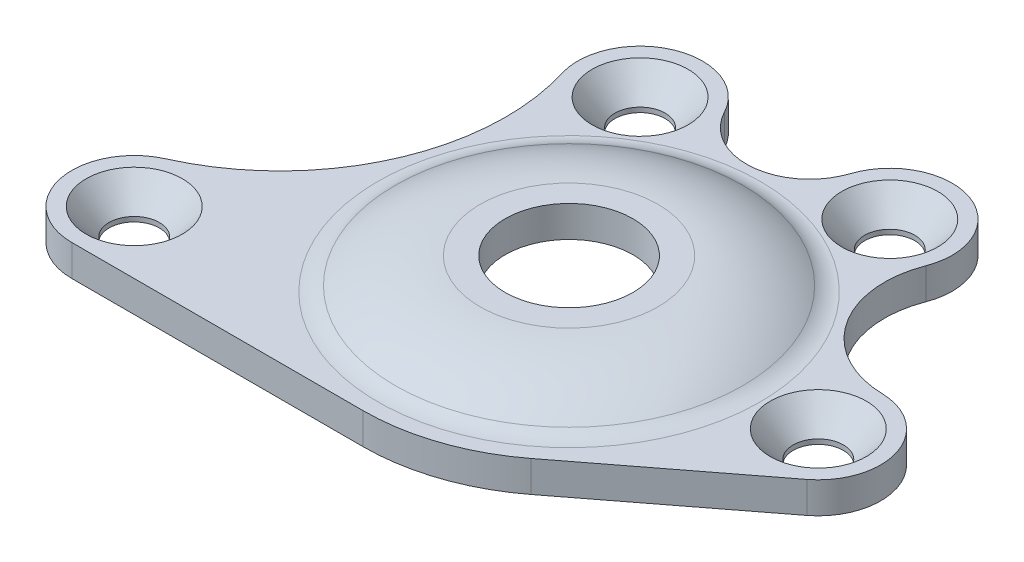
SolidWorks part; units mm, degrees
material "Alum Plate"
ref_plane "Front Plane" through (0, 0, 0) normal (0, 0, 1) x (1, 0, 0)
ref_plane "Top Plane" through (0, 0, 0) normal (0, 1, 0) x (1, 0, 0)
ref_plane "Right Plane" through (0, 0, 0) normal (1, 0, 0) x (0, 0, -1)
sketch "Top Layout" plane through (0, 0, 0) normal (0, 1, 0) x (1, 0, 0)
  line L0 (-114.046, -123.825) -> (-104.775, -123.825) construction
  line L1 (-104.775, -142.875) -> (-101.6, -142.875)
  line L2 (-104.775, -142.875) -> (-104.775, -104.775)
  line L3 (-104.775, -104.775) -> (-101.6, -104.775)
  line L4 (-101.6, -142.875) -> (-101.6, -104.775)
  line L5 (-104.775, -142.875) -> (-101.6, -104.775) construction
  line L6 (-104.775, -104.775) -> (-101.6, -142.875) construction
  line L7 (-19.05, -105.8164) -> (-101.6, -105.8164)
  line L8 (-19.05, -105.8164) -> (-19.05, -141.8336)
  line L9 (-19.05, -141.8336) -> (-101.6, -141.8336)
  line L10 (-101.6, -105.8164) -> (-101.6, -141.8336)
  line L11 (-19.05, -105.8164) -> (-101.6, -141.8336) construction
  line L12 (-19.05, -141.8336) -> (-101.6, -105.8164) construction
  line L13 (-133.096, -85.725) -> (-114.046, -85.725)
  line L14 (-133.096, -85.725) -> (-133.096, -161.925)
  line L15 (-133.096, -161.925) -> (-114.046, -161.925)
  line L16 (-114.046, -85.725) -> (-114.046, -161.925)
  line L17 (-133.096, -85.725) -> (-114.046, -161.925) construction
  line L18 (-133.096, -161.925) -> (-114.046, -85.725) construction
  line L19 (-104.775, -123.825) -> (0, -123.825) construction
  line L20 (0, -123.825) -> (0, 0) construction
  line L21 (-52.3528, -40.1717) -> (0, 0) construction
  line L22 (-70.6449, -16.3328) -> (-18.2922, 23.8388)
  line L23 (-34.0606, -64.0105) -> (18.2922, -23.8388)
  line L24 (-30.9251, 40.3023) -> (-122.2248, -29.7544)
  line L25 (-153.9748, -53.975) -> (-153.9748, -123.825)
  line L26 (-109.5248, -162.052) -> (109.5248, -162.052)
  line L27 (0, -162.052) -> (0, -123.825) construction
  line L28 (-109.5248, -162.052) -> (-109.5248, -20.0093) construction
  line L29 (-104.775, -142.875) -> (-104.775, -152.527)
  line L30 (-104.775, -152.527) -> (104.775, -152.527)
  line L31 (104.775, -104.775) -> (101.6, -104.775)
  line L32 (-144.4498, -73.025) -> (-109.5248, -73.025)
  line L33 (-144.4498, -73.025) -> (-144.4498, -123.825)
  line L34 (-144.4498, -123.825) -> (-109.5248, -123.825) construction
  line L35 (-109.5248, -73.025) -> (-109.5248, -162.052)
  line L36 (-144.4498, -73.025) -> (-109.5248, -123.825) construction
  line L37 (-144.4498, -123.825) -> (-109.5248, -73.025) construction
  line L38 (101.6, -142.875) -> (101.6, -104.775)
  line L39 (104.775, -142.875) -> (101.6, -142.875)
  line L40 (104.775, -142.875) -> (104.775, -104.775)
  line L41 (104.775, -142.875) -> (104.775, -152.527)
  line L42 (109.5248, -162.052) -> (109.5248, -20.0093) construction
  line L43 (30.9251, 40.3023) -> (122.2248, -29.7544)
  line L45 (19.05, -141.8336) -> (101.6, -141.8336)
  line L46 (101.6, -105.8164) -> (101.6, -141.8336)
  line L47 (19.05, -105.8164) -> (101.6, -105.8164)
  line L48 (19.05, -105.8164) -> (19.05, -141.8336)
  line L49 (133.096, -161.925) -> (114.046, -161.925)
  line L50 (114.046, -85.725) -> (114.046, -161.925)
  line L51 (133.096, -85.725) -> (114.046, -85.725)
  line L52 (133.096, -85.725) -> (133.096, -161.925)
  line L53 (144.4498, -123.825) -> (109.5248, -123.825) construction
  line L54 (109.5248, -73.025) -> (109.5248, -162.052)
  line L55 (144.4498, -73.025) -> (109.5248, -73.025)
  line L56 (144.4498, -73.025) -> (144.4498, -123.825)
  line L57 (-109.5248, -123.825) -> (-109.5248, -162.052) construction
  line L62 (-153.9748, -53.975) -> (-122.2248, -53.975)
  line L63 (-122.2248, -53.975) -> (-122.2248, -29.7544)
  line L64 (-144.4498, -123.825) -> (-153.9748, -123.825)
  line L65 (153.9748, -53.975) -> (153.9748, -123.825)
  line L66 (109.5248, -123.825) -> (109.5248, -162.052) construction
  line L67 (144.4498, -123.825) -> (153.9748, -123.825)
  line L68 (122.2248, -29.7544) -> (122.2248, -53.975)
  line L73 (-104.775, -104.775) -> (-104.775, -16.3647) construction
  line L74 (-95.25, -162.052) -> (-95.25, -9.0559) construction
  line L75 (-109.5248, -162.052) -> (-109.5248, -123.825) construction
  line L76 (109.5248, -162.052) -> (109.5248, -123.825) construction
  line L77 (122.2248, -53.975) -> (153.9748, -53.975)
  line L83 (104.775, -155.5496) -> (-104.775, -155.5496) construction
  line L88 (95.25, -162.052) -> (95.25, -9.0559) construction
  line L89 (104.775, -104.775) -> (104.775, -16.3647) construction
  line L92 (-104.775, -152.527) -> (-104.775, -162.052) construction
  line L93 (-14.605, -76.327) -> (14.605, -76.327)
  line L94 (-14.605, -76.327) -> (-14.605, -152.527)
  line L95 (-14.605, -152.527) -> (14.605, -152.527)
  line L96 (14.605, -76.327) -> (14.605, -152.527)
  line L97 (-14.605, -76.327) -> (14.605, -152.527) construction
  line L98 (-14.605, -152.527) -> (14.605, -76.327) construction
  line L99 (104.775, -152.527) -> (104.775, -162.052) construction
  line L100 (-19.05, -105.8164) -> (0, -105.8164) construction
  line L107 (0, -105.8164) -> (19.05, -105.8164) construction
  line L108 (104.775, -123.825) -> (114.046, -123.825) construction
  circle A0 centre (0, 0) radius 114.3
  circle A1 centre (0, 0) radius 6.35
  circle A2 centre (-52.3528, -40.1717) radius 17.8
  circle A3 centre (0, 0) radius 30.0482
  circle A4 centre (-52.3528, -40.1717) radius 30.0482
  arc A5 (-30.9251, 40.3023) -> (30.9251, 40.3023) centre (0, 0) cw
  point P2 (-103.1875, -123.825)
  point P7 (-60.325, -123.825)
  point P12 (-123.571, -123.825)
  point P30 (-126.9873, -98.425)
  point P35 (0, -114.427)
  point P53 (0, -152.527)
  dimension "D1" = 35.6
  dimension "D2" = 12.7
  dimension "D3" = 228.6
  dimension "D11" = 60.0964
  dimension "D12" = 50.8
  dimension "D14" = 52.5
  dimension "D4" = 3.175
  dimension "D5" = 19.05
  dimension "D6" = 76.2
  dimension "D7" = 82.55
  dimension "D8" = 38.1
  dimension "D9" = 104.775
  dimension "D10" = 18.0086
  dimension "D13" = 9.525
  dimension "D15" = 4.7498
  dimension "D16" = 9.525
  dimension "D17" = 9.652
  dimension "D18" = 50.8
  dimension "D19" = 12.446
  dimension "D20" = 65.9892
  dimension "D21" = 19.05
  dimension "D22" = 34.925
  dimension "D23" = 123.825
  dimension "D24" = 12.7
  dimension "D25" = 9.525
  dimension "D26" = 29.21
  dimension "D27" = 76.2
  dimension "D28" = 3.0226
sketch "Side Layout" plane through (0, 0, 0) normal (1, 0, 0) x (0, 0, -1)
  line L0 (0, -38.1) -> (0, 33.7344) construction
  line L1 (-114.3, -20.955) -> (114.3, -20.955)
  line L2 (-114.3, -20.955) -> (-114.3, -33.655)
  line L3 (-114.3, -33.655) -> (114.3, -33.655)
  line L4 (114.3, -20.955) -> (114.3, -33.655)
  line L5 (-114.3, -20.955) -> (114.3, -33.655) construction
  line L6 (-114.3, -33.655) -> (114.3, -20.955) construction
  line L7 (-9.525, -32.9406) -> (9.525, -32.9406)
  line L8 (-9.525, -32.9406) -> (-9.525, -38.1)
  line L9 (-9.525, -38.1) -> (9.525, -38.1)
  line L10 (9.525, -32.9406) -> (9.525, -38.1)
  line L11 (-9.525, -32.9406) -> (9.525, -38.1) construction
  line L12 (-9.525, -38.1) -> (9.525, -32.9406) construction
  line L13 (-11.9126, -29.3338) -> (11.9126, -29.3338)
  line L14 (-11.9126, -29.3338) -> (-11.9126, -32.9406)
  line L15 (-11.9126, -32.9406) -> (11.9126, -32.9406)
  line L16 (11.9126, -29.3338) -> (11.9126, -32.9406)
  line L17 (-11.9126, -29.3338) -> (11.9126, -32.9406) construction
  line L18 (-11.9126, -32.9406) -> (11.9126, -29.3338) construction
  line L19 (-6.35, -32.9406) -> (6.35, -32.9406)
  line L20 (-6.35, -32.9406) -> (-6.35, 33.7344)
  line L21 (-6.35, 33.7344) -> (6.35, 33.7344)
  line L22 (6.35, -32.9406) -> (6.35, 33.7344)
  line L23 (-6.35, -32.9406) -> (6.35, 33.7344) construction
  line L24 (-6.35, 33.7344) -> (6.35, -32.9406) construction
  line L25 (-162.052, 0) -> (-123.825, 0) construction
  line L26 (114.3, -33.655) -> (114.3, 0) construction
  line L27 (-142.875, 19.05) -> (-104.775, 19.05)
  line L28 (-40.1717, -9.525) -> (-40.1717, 5.4) construction
  line L29 (-142.875, 19.05) -> (-142.875, -19.05)
  line L30 (-142.875, -19.05) -> (-104.775, -19.05)
  line L31 (-104.775, 19.05) -> (-104.775, -19.05)
  line L32 (-142.875, 19.05) -> (-104.775, -19.05) construction
  line L33 (-142.875, -19.05) -> (-104.775, 19.05) construction
  line L34 (-130.175, -38.1) -> (-117.9516, -38.1) construction
  line L35 (-57.9717, -14.6) -> (-22.3717, -14.6)
  line L36 (-30.0482, -2.794) -> (30.0482, -2.794)
  line L37 (-30.0482, -2.794) -> (-30.0482, -20.955)
  line L38 (-30.0482, -20.955) -> (30.0482, -20.955)
  line L39 (30.0482, -2.794) -> (30.0482, -20.955)
  line L40 (-30.0482, -2.794) -> (30.0482, -20.955) construction
  line L41 (-30.0482, -20.955) -> (30.0482, -2.794) construction
  line L42 (-30.0482, -2.794) -> (-30.0482, 0) construction
  line L43 (-123.825, 0) -> (0, 0) construction
  line L44 (-57.9717, -14.6) -> (-57.9717, 25.4)
  line L45 (-57.9717, 25.4) -> (-22.3717, 25.4)
  line L46 (-22.3717, -14.6) -> (-22.3717, 25.4)
  line L47 (-19.05, 0) -> (19.05, 0)
  line L48 (-19.05, 0) -> (-19.05, -1.9812)
  line L49 (-19.05, -1.9812) -> (19.05, -1.9812)
  line L50 (19.05, 0) -> (19.05, -1.9812)
  line L51 (-19.05, 0) -> (19.05, -1.9812) construction
  line L52 (-19.05, -1.9812) -> (19.05, 0) construction
  line L53 (-70.2199, -3.175) -> (-10.1235, -3.175)
  line L54 (-70.2199, -3.175) -> (-70.2199, -15.875)
  line L55 (-70.2199, -15.875) -> (-10.1235, -15.875)
  line L56 (-10.1235, -3.175) -> (-10.1235, -15.875)
  line L57 (-70.2199, -3.175) -> (-10.1235, -15.875) construction
  line L58 (-70.2199, -15.875) -> (-10.1235, -3.175) construction
  line L59 (-40.1717, -9.525) -> (-40.1717, 0) construction
  line L60 (-57.9717, -14.6) -> (-22.3717, 25.4) construction
  line L61 (-57.9717, 25.4) -> (-22.3717, -14.6) construction
  line L62 (-22.3717, 0) -> (-57.9717, 0) construction
  line L63 (-137.8162, 0) -> (-123.825, -13.9912) construction
  line L64 (-139.065, 15.24) -> (-108.585, 15.24) construction
  line L65 (-139.065, 15.24) -> (-139.065, -15.24) construction
  line L66 (-139.065, -15.24) -> (-108.585, -15.24) construction
  line L67 (-108.585, 15.24) -> (-108.585, -15.24) construction
  line L68 (-139.065, 15.24) -> (-108.585, -15.24) construction
  line L69 (-139.065, -15.24) -> (-108.585, 15.24) construction
  line L70 (-137.8162, 0) -> (-123.825, 13.9912) construction
  line L71 (-123.825, -13.9912) -> (-109.8338, 0) construction
  line L72 (-123.825, 13.9912) -> (-109.8338, 0) construction
  line L73 (-137.8162, 0) -> (-109.8338, 0) construction
  line L74 (-123.825, -13.9912) -> (-123.825, 13.9912) construction
  line L75 (-6.35, 17.8594) -> (6.35, 17.8594)
  line L76 (114.3, 0) -> (-114.3, 0) construction
  line L77 (-22.3717, 19.05) -> (-6.35, 19.05) construction
  line L78 (-123.825, 38.1) -> (-97.9206, 38.1) construction
  line L79 (-19.05, -3.5814) -> (19.05, -3.5814)
  line L80 (-19.05, -3.5814) -> (-19.05, -1.9812)
  line L81 (-19.05, -1.9812) -> (19.05, -1.9812)
  line L82 (19.05, -3.5814) -> (19.05, -1.9812)
  line L83 (-19.05, -3.5814) -> (19.05, -1.9812) construction
  line L84 (-19.05, -1.9812) -> (19.05, -3.5814) construction
  line L85 (-8.7376, -16.7608) -> (8.7376, -16.7608)
  line L86 (-8.7376, -16.7608) -> (-8.7376, -29.3338)
  line L87 (-8.7376, -29.3338) -> (8.7376, -29.3338)
  line L88 (8.7376, -16.7608) -> (8.7376, -29.3338)
  line L89 (-8.7376, -16.7608) -> (8.7376, -29.3338) construction
  line L90 (-8.7376, -29.3338) -> (8.7376, -16.7608) construction
  line L91 (-8.7376, -3.5814) -> (8.7376, -3.5814)
  line L92 (-8.7376, -3.5814) -> (-8.7376, -16.1544)
  line L93 (-8.7376, -16.1544) -> (8.7376, -16.1544)
  line L94 (8.7376, -3.5814) -> (8.7376, -16.1544)
  line L95 (-8.7376, -3.5814) -> (8.7376, -16.1544) construction
  line L96 (-8.7376, -16.1544) -> (8.7376, -3.5814) construction
  circle A0 centre (-123.825, 0) radius 18.0086
  circle A1 centre (-123.825, 0) radius 38.1
  circle A2 centre (-139.065, 15.24) radius 1.905
  circle A3 centre (-108.585, 15.24) radius 1.905
  circle A4 centre (-108.585, -15.24) radius 1.905
  circle A5 centre (-139.065, -15.24) radius 1.905
  circle A6 centre (-137.8162, 0) radius 1.6002
  circle A7 centre (-123.825, 13.9912) radius 1.6002
  circle A8 centre (-109.8338, 0) radius 1.6002
  circle A9 centre (-123.825, -13.9912) radius 1.6002
  point P0 (0, -27.305)
  point P6 (0, -31.1372)
  point P7 (0, -35.5203)
  point P21 (0, 0.3969)
  point P32 (0, -11.8745)
  point P43 (0, -0.9906)
  point P55 (-40.1717, -9.525)
  point P72 (-40.1717, 5.4)
  point P88 (0, -23.0473)
  point P93 (0, -2.7813)
  point P102 (0, -9.8679)
  dimension "D17" = 3.81
  dimension "D18" = 3.2004
  dimension "D1" = 12.7
  dimension "D2" = 5.1594
  dimension "D3" = 19.05
  dimension "D4" = 3.6068
  dimension "D5" = 23.8252
  dimension "D6" = 12.7
  dimension "D7" = 18.161
  dimension "D8" = 1.9812
  dimension "D9" = 12.7
  dimension "D10" = 40
  dimension "D11" = 25.4
  dimension "D12" = 50.8
  dimension "D13" = 41.275
  dimension "D14" = 30.48
  dimension "D15" = 4.445
  dimension "D16" = 19.7866
  dimension "D19" = 15.875
  dimension "D20" = 6.35
  dimension "D21" = 38.1
  dimension "D22" = 1.6002
  dimension "D23" = 38.1
  dimension "D24" = 17.4752
  dimension "D25" = 12.573
ref_plane "Plane1" through (0, 25.4, 0) normal (0, 1, 0) x (1, 0, 0)
sketch "Sketch3" plane through (0, 25.4, 0) normal (0, 1, 0) x (1, 0, 0)
  line L0 (-104.775, -36.3747) -> (-30.9251, 20.2924)
  line L1 (-104.775, -104.775) -> (-104.775, -16.3647) construction
  line L2 (0, -200130.175) -> (0, 199882.0484) construction
  line L3 (-30.9251, 40.3023) -> (-122.2248, -29.7544) construction
  line L5 (-104.775, -36.3747) -> (-104.775, -77.6497)
  line L6 (-92.075, -77.6497) -> (-104.775, -77.6497)
  line L7 (30.9251, 20.2924) -> (104.775, -36.3747)
  line L8 (104.775, -77.6497) -> (92.075, -77.6497)
  line L9 (104.775, -36.3747) -> (104.775, -77.6497)
  line L11 (104.775, -104.775) -> (104.775, -16.3647) construction
  line L12 (30.9251, 40.3023) -> (122.2248, -29.7544) construction
  line L13 (92.075, -74.6536) -> (24.1423, -22.5271)
  line L14 (-32.2514, -66.3682) -> (20.1013, -26.1965)
  line L15 (-30.9251, 20.2924) -> (0, 44.022)
  line L16 (0, 44.022) -> (30.9251, 20.2924)
  line L17 (-92.075, -77.6497) -> (-92.075, -73.1917)
  line L19 (-92.075, -73.1917) -> (-52.3528, -73.1917)
  line L20 (92.075, -74.6536) -> (92.075, -77.6497)
  circle A0 centre (-52.3528, -40.1717) radius 17.8 construction
  circle A1 centre (-52.3528, -40.1717) radius 17.8
  circle A2 centre (0, 0) radius 6.35
  circle A3 centre (0, 0) radius 6.35 construction
  arc A4 (-52.3528, -73.1917) -> (-32.2514, -66.3682) centre (-52.3528, -40.1717) ccw
  arc A5 (20.1013, -26.1965) -> (24.1423, -22.5271) centre (0, 0) ccw
  arc A6 (30.9251, 20.2924) -> (-30.9251, 20.2924) centre (0, -20.01) ccw construction
  point P28 (0, 44.022)
  dimension "D1" = 33.02
  dimension "D5" = 50.8
  dimension "D2" = 41.275
  dimension "D3" = 34.925
  dimension "D4" = 12.7
  dimension "D6" = 38.1
extrude "Boss-Extrude1" [suppressed] add sketch "Sketch3" against normal blind 6.35
ref_plane "Plane3" through (-104.775, 0, 0) normal (-1, 0, 0) x (0, 0, 1)
sketch "Sketch6" plane through (-104.775, 0, 0) normal (-1, 0, 0) x (0, 0, 1)
  line L0 (162.052, -25.4) -> (162.052, 25.4)
  line L1 (162.052, 25.4) -> (77.6497, 25.4)
  line L2 (36.3747, 25.4) -> (77.6497, 25.4) construction
  line L3 (147.7645, 11.1125) -> (162.052, 11.1125) construction
  line L4 (162.052, 0) -> (71.2997, 0) construction
  line L5 (77.6497, 25.4) -> (77.6497, 19.05)
  line L6 (77.6497, 19.05) -> (36.3747, 19.05)
  line L7 (36.3747, 19.05) -> (36.3747, 6.35)
  line L8 (36.3747, 6.35) -> (71.2997, 6.35)
  line L10 (99.6315, -3.175) -> (99.6315, 11.1125) construction
  line L11 (71.2997, -25.4) -> (162.052, -25.4)
  line L13 (71.2997, 6.35) -> (71.2997, -25.4)
  line L14 (152.527, -25.4) -> (152.527, 25.4) construction
  line L15 (99.6315, 11.1125) -> (99.6315, 25.4) construction
  line L16 (147.7645, 11.1125) -> (147.7645, 25.4) construction
  line L17 (94.869, -7.9375) -> (104.394, -7.9375) construction
  line L18 (94.869, -7.9375) -> (94.869, 25.4) construction
  line L19 (94.869, 25.4) -> (104.394, 25.4) construction
  line L20 (104.394, -7.9375) -> (104.394, 25.4) construction
  line L21 (94.869, -7.9375) -> (104.394, 25.4) construction
  line L22 (94.869, 25.4) -> (104.394, -7.9375) construction
  line L23 (147.7645, 11.1125) -> (147.7645, -3.175) construction
  line L24 (104.394, -7.9375) -> (123.825, -7.9375) construction
  line L25 (143.002, -7.9375) -> (152.527, -7.9375) construction
  line L26 (143.002, -7.9375) -> (143.002, 25.4) construction
  line L27 (143.002, 25.4) -> (152.527, 25.4) construction
  line L28 (152.527, -7.9375) -> (152.527, 25.4) construction
  line L29 (143.002, -7.9375) -> (152.527, 25.4) construction
  line L30 (143.002, 25.4) -> (152.527, -7.9375) construction
  line L31 (123.825, -7.9375) -> (152.527, -7.9375) construction
  line L32 (104.775, 19.05) -> (104.775, -19.05) construction
  line L34 (155.702, -25.4) -> (155.702, 25.4) construction
  circle A0 centre (109.8338, 0) radius 1.6002 construction
  circle A1 centre (123.825, 13.9912) radius 1.6002 construction
  circle A2 centre (137.8162, 0) radius 1.6002 construction
  circle A3 centre (123.825, -13.9912) radius 1.6002 construction
  circle A4 centre (109.8338, 0) radius 1.6002 construction
  circle A5 centre (123.825, 13.9912) radius 1.6002 construction
  circle A6 centre (137.8162, 0) radius 1.6002 construction
  circle A7 centre (123.825, -13.9912) radius 1.6002 construction
  circle A8 centre (123.825, 0) radius 18.0086 construction
  circle A9 centre (123.825, 0) radius 18.0086 construction
  circle A10 centre (123.825, 0) radius 9.525
  circle A11 centre (108.585, -15.24) radius 1.905 construction
  circle A12 centre (108.585, 15.24) radius 1.905 construction
  circle A13 centre (139.065, 15.24) radius 1.905 construction
  circle A14 centre (139.065, -15.24) radius 1.905 construction
  circle A15 centre (108.585, -15.24) radius 1.905
  circle A16 centre (108.585, 15.24) radius 1.905
  circle A17 centre (139.065, 15.24) radius 1.905
  circle A18 centre (139.065, -15.24) radius 1.905
  circle A19 centre (147.7645, 11.1125) radius 2.5527
  circle A26 centre (99.6315, 11.1125) radius 2.5527
  circle A27 centre (99.6315, -3.175) radius 2.5527
  circle A28 centre (147.7645, -3.175) radius 2.5527
  point P29 (0, 0)
  point P55 (99.6315, 8.7312)
  point P61 (147.7645, 8.7312)
  dimension "D4" = 19.05
  dimension "D7" = 5.1054
  dimension "D1" = 6.35
  dimension "D2" = 12.7
  dimension "D3" = 25.4
  dimension "D5" = 6.35
  dimension "D6" = 3.175
  dimension "D8" = 0.381
  dimension "D9" = 14.2875
  dimension "D10" = 9.525
  dimension "D12" = 33.3375
extrude "Side Plate Extrude" [suppressed] add sketch "Sketch6" along normal up to vertex up to point (-109.5248, 0, 73.025)
ref_plane "Plane4" through (0, 19.05, 0) normal (0, 1, 0) x (1, 0, 0)
sketch "Sketch12" plane through (0, 19.05, 0) normal (0, 1, 0) x (1, 0, 0)
  line L0 (-104.775, -77.6497) -> (-104.775, -36.3747)
  line L1 (-104.775, -36.3747) -> (-92.075, -36.3747)
  line L3 (-92.075, -36.3747) -> (-92.075, -77.6497)
  line L5 (-92.075, -77.6497) -> (-104.775, -77.6497)
  line L6 (-98.425, -77.6497) -> (-98.425, -63.3622) construction
  line L7 (-98.425, -63.3622) -> (-98.425, -50.6622) construction
  line L8 (-98.425, -50.6622) -> (-98.425, -36.3747) construction
  line L10 (-98.425, -36.3747) -> (-104.775, -36.3747) construction
  circle A0 centre (-98.425, -63.3622) radius 2.5527
  circle A1 centre (-98.425, -50.6622) radius 2.5527
  dimension "D2" = 5.1054
  dimension "D1" = 12.7
  dimension "D3" = 12.7
sketch "Sketch24" [suppressed] plane through (0, -12.7, 0) normal (0, -1, 0) x (1, 0, 0)
  line L5 (-104.775, 94.8709) -> (-104.775, 152.527)
  line L7 (-104.775, 152.527) -> (104.775, 152.527)
  line L9 (104.775, 152.527) -> (104.775, 94.8709)
  line L10 (-99.695, 92.4539) -> (-99.695, 94.8709)
  line L12 (-104.775, 94.8709) -> (-104.775, 77.6497)
  line L28 (104.775, 77.6497) -> (104.775, 94.8709)
  line L45 (104.775, 77.6497) -> (104.775, 94.8709)
  line L47 (-104.775, 94.8709) -> (-104.775, 77.6497)
  line L48 (-104.775, 77.6497) -> (-92.075, 77.6497)
  line L49 (-104.775, 77.6497) -> (-92.075, 77.6497)
  line L51 (89.9708, 82.7297) -> (86.995, 82.7297)
  line L52 (92.075, 77.6497) -> (104.775, 77.6497)
  line L53 (92.075, 77.6497) -> (104.775, 77.6497)
  line L54 (99.695, 94.8709) -> (99.695, 92.4539)
  line L56 (28.6663, 26.0276) -> (-29.1589, 70.3984)
  line L57 (-86.995, 82.7297) -> (-89.9708, 82.7297)
  line L58 (19.9724, 26.2955) -> (20.1013, 26.1965)
  line L59 (19.9724, 26.2955) -> (20.1013, 26.1965)
  line L60 (-99.695, 94.8709) -> (-104.775, 94.8709)
  line L61 (104.775, 94.8709) -> (99.695, 94.8709)
  line L74 (86.995, 82.7297) -> (86.995, 77.1588)
  line L76 (86.995, 77.1588) -> (31.7579, 34.7739)
  line L78 (-52.3528, 78.2717) -> (-86.995, 78.2717)
  line L79 (-32.2514, 66.3682) -> (19.7754, 26.4466)
  line L80 (-86.995, 78.2717) -> (-86.995, 82.7297)
  line L82 (-92.075, 77.6497) -> (-92.075, 73.1917)
  line L83 (-92.075, 77.6497) -> (-92.075, 73.1917)
  line L84 (-92.075, 73.1917) -> (-52.3528, 73.1917)
  line L85 (-92.075, 73.1917) -> (-52.3528, 73.1917)
  line L86 (24.1423, 22.5271) -> (92.075, 74.6536)
  line L87 (24.1423, 22.5271) -> (92.075, 74.6536)
  line L88 (92.075, 74.6536) -> (92.075, 77.6497)
  line L89 (92.075, 74.6536) -> (92.075, 77.6497)
  line L90 (-32.2514, 66.3682) -> (19.7754, 26.4466)
  line L91 (19.7754, 26.4466) -> (19.9724, 26.2955)
  line L92 (19.7754, 26.4466) -> (19.9724, 26.2955)
  circle A0 centre (-97.155, 85.2697) radius 4.826 construction
  circle A1 centre (-97.155, 85.2697) radius 2.4892
  circle A6 centre (97.155, 85.2697) radius 2.4892
  circle A7 centre (24.5121, 32.4156) radius 2.4892
  arc A9 (99.695, 92.4539) -> (89.9708, 82.7297) centre (97.155, 85.2697) ccw
  circle A11 centre (24.5121, 32.4156) radius 4.826 construction
  arc A17 (-89.9708, 82.7297) -> (-99.695, 92.4539) centre (-97.155, 85.2697) ccw
  arc A18 (-29.1589, 70.3984) -> (-52.3528, 78.2717) centre (-52.3528, 40.1717) ccw
  arc A19 (31.7579, 34.7739) -> (28.6663, 26.0276) centre (24.5121, 32.4156) ccw
  arc A20 (-32.2514, 66.3682) -> (-52.3528, 73.1917) centre (-52.3528, 40.1717) ccw
  arc A21 (24.1423, 22.5271) -> (20.1013, 26.1965) centre (0, 0) ccw
  arc A22 (24.1423, 22.5271) -> (20.1013, 26.1965) centre (0, 0) ccw
  arc A30 (-32.2514, 66.3682) -> (-52.3528, 73.1917) centre (-52.3528, 40.1717) ccw
  dimension "D3" = 4.9784
  dimension "D1" = 0
sketch "Sketch38" [suppressed] plane through (-104.775, 0, 0) normal (-1, 0, 0) x (0, 0, 1)
  line L1 (152.527, -7.9375) -> (143.002, -7.9375)
  line L2 (152.527, -7.9375) -> (152.527, 25.4)
  line L3 (152.527, 25.4) -> (143.002, 25.4)
  line L4 (143.002, -7.9375) -> (143.002, 25.4)
  line L5 (152.527, -7.9375) -> (143.002, 25.4) construction
  line L6 (152.527, 25.4) -> (143.002, -7.9375) construction
  point P4 (147.7645, 8.7312)
extrude "Cut-Extrude16" [suppressed] cut sketch "Sketch38" against normal blind 9.525
sketch "Sketch46" [suppressed] plane through (-104.775, 0, 0) normal (-1, 0, 0) x (0, 0, 1)
  line L0 (142.875, 19.05) -> (104.775, -19.05) construction
  line L1 (104.14, 19.685) -> (143.51, 19.685)
  line L2 (104.14, 19.685) -> (104.14, -19.685)
  line L3 (104.14, -19.685) -> (143.51, -19.685)
  line L4 (143.51, 19.685) -> (143.51, -19.685)
  line L5 (104.14, 19.685) -> (143.51, -19.685) construction
  line L6 (104.14, -19.685) -> (143.51, 19.685) construction
  point P0 (123.825, 0)
  dimension "D1" = 39.37
extrude "Cut-Extrude21" [suppressed] cut sketch "Sketch46" against normal blind 6.985
ref_plane "Plane5" through (0, 0, 152.527) normal (0, 0, 1) x (1, 0, 0)
sketch "Sketch41" plane through (0, 0, 152.527) normal (0, 0, 1) x (1, 0, 0)
  line L0 (-104.775, -7.9375) -> (-104.775, 25.4) construction
  line L1 (-104.775, -7.9375) -> (-104.775, 12.7)
  line L2 (-104.775, -7.9375) -> (104.775, -7.9375)
  line L3 (104.775, -7.9375) -> (104.775, 12.7)
  line L4 (104.775, 25.4) -> (-104.775, 25.4)
  line L5 (0, -7.9375) -> (0, 25.4) construction
  line L6 (-104.775, 3.9624) -> (-100.0125, 3.9624) construction
  line L7 (-100.0125, 3.9624) -> (-100.0125, 25.4) construction
  line L8 (104.775, 3.9624) -> (100.0125, 3.9624) construction
  line L9 (100.0125, 3.9624) -> (100.0125, 25.4) construction
  line L10 (19.05, 20.6375) -> (23.8252, 20.6375) construction
  line L11 (19.05, 15.875) -> (78.5876, 15.875) construction
  line L12 (19.05, 15.875) -> (19.05, 25.4) construction
  line L13 (19.05, 25.4) -> (78.5876, 25.4) construction
  line L14 (78.5876, 15.875) -> (78.5876, 25.4) construction
  line L15 (19.05, 15.875) -> (78.5876, 25.4) construction
  line L16 (19.05, 25.4) -> (78.5876, 15.875) construction
  line L17 (23.8252, 20.6375) -> (38.1127, 20.6375) construction
  line L18 (38.1127, 20.6375) -> (52.4002, 20.6375) construction
  line L19 (52.4002, 20.6375) -> (66.6877, 20.6375) construction
  line L20 (-104.775, 25.4) -> (-112.395, 25.4)
  line L21 (-112.395, 25.4) -> (-112.395, 3.175)
  line L22 (-112.395, 3.175) -> (-109.5248, 3.175)
  line L23 (-109.5248, 3.175) -> (-109.5248, 12.7)
  line L24 (-109.5248, 12.7) -> (-104.775, 12.7)
  line L25 (-104.775, 12.7) -> (-104.775, 25.4) construction
  line L26 (104.775, 25.4) -> (112.395, 25.4)
  line L27 (112.395, 25.4) -> (112.395, 3.175)
  line L28 (112.395, 3.175) -> (109.5248, 3.175)
  line L29 (109.5248, 3.175) -> (109.5248, 12.7)
  line L30 (109.5248, 12.7) -> (104.775, 12.7)
  line L31 (104.775, 12.7) -> (104.775, 25.4) construction
  line L32 (-100.0125, 3.9624) -> (-87.3125, 3.9624) construction
  line L33 (-63.5, -1.5875) -> (0, -1.5875) construction
  line L34 (0, -1.5875) -> (63.5, -1.5875) construction
  line L35 (63.5, -1.5875) -> (63.5, -7.9375) construction
  circle A0 centre (-100.0125, 3.9624) radius 2.5527
  circle A1 centre (100.0125, 3.9624) radius 2.5527
  circle A2 centre (23.8252, 20.6375) radius 2.5527
  circle A3 centre (38.1127, 20.6375) radius 2.5527
  circle A4 centre (52.4002, 20.6375) radius 2.5527
  circle A5 centre (66.6877, 20.6375) radius 2.5527
  circle A6 centre (-66.6877, 20.6375) radius 2.5527
  circle A7 centre (-52.4002, 20.6375) radius 2.5527
  circle A8 centre (-38.1127, 20.6375) radius 2.5527
  circle A9 centre (-23.8252, 20.6375) radius 2.5527
  circle A10 centre (-87.3125, 3.9624) radius 2.5527
  circle A11 centre (87.3125, 3.9624) radius 2.5527
  circle A12 centre (-63.5, -1.5875) radius 2.5527
  circle A13 centre (63.5, -1.5875) radius 2.5527
  point P14 (48.8188, 20.6375)
  dimension "D3" = 5.1054
  dimension "D7" = 5.1054
  dimension "D1" = 21.4376
  dimension "D2" = 4.7625
  dimension "D4" = 9.525
  dimension "D5" = 59.5376
  dimension "D6" = 4.7752
  dimension "D8" = 14.2875
  dimension "D9" = 7.62
  dimension "D10" = 4.7498
  dimension "D11" = 12.7
  dimension "D12" = 9.525
  dimension "D13" = 19.05
  dimension "D14" = 12.7
  dimension "D15" = 6.35
  dimension "D16" = 63.5
sketch "Sketch43" [suppressed] plane through (-109.5248, 0, 0) normal (-1, 0, 0) x (0, 0, 1)
  line L1 (152.527, 12.7) -> (155.702, 12.7)
  line L2 (152.527, 12.7) -> (152.527, 25.4)
  line L3 (152.527, 25.4) -> (155.702, 25.4)
  line L4 (155.702, 12.7) -> (155.702, 25.4)
  line L5 (152.527, 12.7) -> (155.702, 25.4) construction
  line L6 (152.527, 25.4) -> (155.702, 12.7) construction
  line L7 (162.052, 25.4) -> (77.6497, 25.4) construction
  point P4 (154.1145, 19.05)
  dimension "D1" = 3.175
sketch "Sketch44" plane through (0, 25.4, 0) normal (0, 1, 0) x (1, 0, 0)
  line L0 (73.8315, -147.7645) -> (73.8315, -152.527) construction
  line L1 (92.075, -74.6536) -> (92.075, -77.6497) construction
  line L2 (-92.075, -77.6497) -> (-92.075, -73.1917) construction
  line L3 (0, -123.825) -> (0, 0) construction
  line L4 (-92.075, -73.1917) -> (-52.3528, -73.1917) construction
  line L5 (-104.775, -104.775) -> (-104.775, -16.3647) construction
  line L6 (-32.2514, -66.3682) -> (20.1013, -26.1965) construction
  line L21 (-104.775, -68.1247) -> (-104.775, -152.527)
  line L22 (-104.775, -152.527) -> (104.775, -152.527)
  line L23 (104.775, -152.527) -> (104.775, -68.1247)
  line L34 (-104.775, -99.6315) -> (-100.0125, -99.6315) construction
  line L35 (-104.775, -147.7645) -> (-100.0125, -147.7645) construction
  line L36 (0, -152.527) -> (0, -35.6178) construction
  line L38 (30.969, -147.7645) -> (45.2565, -147.7645) construction
  line L39 (45.2565, -147.7645) -> (59.544, -147.7645) construction
  line L40 (59.544, -147.7645) -> (73.8315, -147.7645) construction
  line L41 (23.8252, -152.527) -> (30.969, -152.527) construction
  line L42 (104.775, -152.527) -> (-104.775, -152.527) construction
  line L43 (30.969, -152.527) -> (38.1127, -152.527) construction
  line L44 (30.969, -152.527) -> (30.969, -147.7645) construction
  line L45 (-92.075, -77.6497) -> (-104.775, -77.6497) construction
  line L48 (-35.1507, -62.5899) -> (-8.9743, -42.504) construction
  line L49 (-8.9743, -42.504) -> (17.2021, -22.4182) construction
  line L50 (45.5313, -32.9364) -> (87.3125, -64.9962) construction
  line L51 (92.075, -74.6536) -> (24.1423, -22.5271) construction
  line L52 (104.775, -77.6497) -> (92.075, -77.6497) construction
  line L79 (-104.775, -68.1247) -> (-92.075, -68.1247)
  line L80 (-92.075, -68.1247) -> (-92.075, -63.6667)
  line L85 (21.8118, -8.7328) -> (92.075, -62.6476)
  line L86 (-38.0499, -58.8115) -> (14.3028, -18.6398)
  line L87 (-92.075, -63.6667) -> (-52.3528, -63.6667)
  line L88 (92.075, -62.6476) -> (92.075, -68.1247)
  line L89 (92.075, -68.1247) -> (104.775, -68.1247)
  circle A0 centre (-73.8315, -147.7645) radius 2.5527
  circle A1 centre (-59.544, -147.7645) radius 2.5527
  circle A2 centre (-45.2565, -147.7645) radius 2.5527
  circle A3 centre (-30.969, -147.7645) radius 2.5527
  circle A17 centre (-100.0125, -99.6315) radius 2.5527
  circle A18 centre (-100.0125, -147.7645) radius 2.5527
  circle A19 centre (100.0125, -147.7645) radius 2.5527
  circle A20 centre (100.0125, -99.6315) radius 2.5527
  circle A21 centre (30.969, -147.7645) radius 2.5527
  circle A22 centre (45.2565, -147.7645) radius 2.5527
  circle A23 centre (59.544, -147.7645) radius 2.5527
  circle A24 centre (73.8315, -147.7645) radius 2.5527
  circle A25 centre (-87.3125, -68.4292) radius 4.7625 construction
  circle A26 centre (-35.1507, -62.5899) radius 4.7625 construction
  circle A27 centre (-8.9743, -42.504) radius 4.7625 construction
  circle A28 centre (17.2021, -22.4182) radius 4.7625 construction
  circle A29 centre (45.5313, -32.9364) radius 4.7625 construction
  circle A30 centre (87.3125, -64.9962) radius 4.7625 construction
  circle A32 centre (-87.3125, -68.4292) radius 2.5527
  circle A33 centre (-35.1507, -62.5899) radius 2.5527
  circle A34 centre (-8.9743, -42.504) radius 2.5527 construction
  circle A35 centre (17.2021, -22.4182) radius 2.5527
  circle A36 centre (45.5313, -32.9364) radius 2.5527
  circle A37 centre (87.3125, -64.9962) radius 2.5527
  circle A38 centre (-97.155, -85.2697) radius 7.62 construction
  circle A39 centre (97.155, -85.2697) radius 7.62 construction
  circle A40 centre (24.5121, -32.4156) radius 7.62 construction
  arc A41 (20.1013, -26.1965) -> (24.1423, -22.5271) centre (0, 0) ccw construction
  circle A42 centre (-97.155, -85.2697) radius 2.5527
  circle A43 centre (24.5121, -32.4156) radius 2.5527
  circle A44 centre (97.155, -85.2697) radius 2.5527
  arc A56 (14.3028, -18.6398) -> (21.8118, -8.7328) centre (0, 0) ccw
  arc A57 (-52.3528, -63.6667) -> (-38.0499, -58.8115) centre (-52.3528, -40.1717) ccw
  point P4 (-104.775, -152.527)
  dimension "D2" = 5.1054
  dimension "D7" = 5.1054
  dimension "D8" = 15.24
  dimension "D3" = 9.525
  dimension "D9" = 9.525
  dimension "D4" = 4.7625
  dimension "D5" = 14.2875
  dimension "D6" = 9.525
  dimension "D1" = 4.7625
  dimension "D10" = 52.664
sketch "Sketch82" [suppressed] plane through (0, 28.829, 0) normal (0, 1, 0) x (1, 0, 0)
  line L0 (-52.3528, -63.6667) -> (-92.075, -63.6667) construction
  line L1 (-52.3528, -65.5717) -> (-52.3528, -63.6667) construction
  line L2 (-12.4467, -41.5667) -> (-13.6064, -40.0553) construction
  line L3 (14.3028, -18.6398) -> (-38.0499, -58.8115) construction
  line L4 (24.5175, -13.2101) -> (25.6772, -11.6988) construction
  line L5 (92.075, -62.6476) -> (21.8118, -8.7328) construction
  line L6 (58.2962, -39.1295) -> (59.4559, -37.6181) construction
  line L7 (21.4643, -9.5551) -> (21.8118, -8.7328)
  line L8 (21.8118, -8.7328) -> (22.2143, -9.0416)
  circle A0 centre (-52.3528, -65.5717) radius 4.7625
  circle A1 centre (-12.4467, -41.5667) radius 4.7625
  arc A2 (21.4643, -9.5551) -> (22.2143, -9.0416) centre (24.5175, -13.2101) ccw
  circle A3 centre (58.2962, -39.1295) radius 4.7625
  arc A4 (14.3028, -18.6398) -> (21.8118, -8.7328) centre (0, 0) ccw construction
  dimension "D1" = 9.525
  dimension "D2" = 1.905
  dimension "D3" = 30.8104
  dimension "D4" = 83.6926
  dimension "D5" = 41.1154
extrude "Cut-Extrude38" [suppressed] cut sketch "Sketch82" against normal up to surface (3.429 mm away)
sketch "Sketch45" [suppressed] plane through (0, -25.4, 0) normal (0, -1, 0) x (1, 0, 0)
  circle A2 centre (24.5121, 32.4156) radius 6.35
  circle A4 centre (-97.155, 85.2697) radius 6.35
  circle A5 centre (97.155, 85.2697) radius 6.35
  dimension "D1" = 12.7
ref_plane "Plane6" through (0, 19.05, 0) normal (0, 1, 0) x (1, 0, 0)
sketch "Sketch59" plane through (0, 19.05, 0) normal (0, 1, 0) x (1, 0, 0)
  line L0 (0, 22.408) -> (0, 30.79) construction
  line L1 (-19.1436, 18.7673) -> (-24.2463, 25.4172) construction
  line L2 (0, 33.4567) -> (-5.1026, 40.1066) construction
  line L3 (-5.1026, 40.1066) -> (-24.2463, 25.4172) construction
  line L4 (-104.775, -36.3747) -> (-30.9251, 20.2924) construction
  line L5 (-19.1436, 18.7673) -> (0, 33.4567) construction
  circle A0 centre (0, 22.408) radius 4.7625
  circle A2 centre (-19.1436, 18.7673) radius 4.7625
  arc A3 (30.9251, 20.2924) -> (-30.9251, 20.2924) centre (0, -20.01) ccw construction
  dimension "D3" = 9.525
  dimension "D1" = 8.382
  dimension "D2" = 24.13
sketch "Sketch47" plane through (0, 25.4, 0) normal (0, 1, 0) x (1, 0, 0)
  line L0 (-21.3485, -42.7945) -> (-23.7291, -44.6212) construction
  line L1 (-81.9672, -61.1267) -> (-75.3534, -61.1267) construction
  line L2 (-19.1436, 18.7673) -> (-38.2872, 4.0779) construction
  line L3 (-38.2872, 4.0779) -> (-57.4308, -10.6115) construction
  line L4 (-57.4308, -10.6115) -> (-76.5745, -25.3009) construction
  line L5 (-19.1436, 18.7673) -> (0, 33.4567) construction
  line L6 (-76.5745, -25.3009) -> (-65.8758, -19.4248) construction
  line L7 (-65.8758, -19.4248) -> (-57.4308, -10.6115) construction
  line L9 (-87.7466, -52.146) -> (-71.6552, -16.7941)
  line L10 (-38.0499, -58.8115) -> (14.3028, -18.6398) construction
  line L11 (-81.9672, -54.7767) -> (-52.3528, -40.1717) construction
  line L12 (-52.3528, -40.1717) -> (-65.8758, -19.4248) construction
  line L13 (-92.075, -63.6667) -> (-52.3528, -63.6667) construction
  line L14 (-70.5066, -49.3452) -> (-83.977, -62.8156) construction
  line L15 (-23.7291, -44.6212) -> (-39.5962, -56.7964)
  line L16 (-52.3528, -61.1267) -> (-81.9672, -61.1267)
  line L17 (-42.4227, -17.4847) -> (-52.3528, -40.1717) construction
  line L18 (-52.3528, -40.1717) -> (-27.5947, -39.5834) construction
  line L19 (-81.9672, -54.7767) -> (-65.8758, -19.4248) construction
  line L20 (-65.8758, -19.4248) -> (-42.4227, -17.4847) construction
  line L21 (-42.4227, -17.4847) -> (-27.5947, -39.5834) construction
  line L22 (-83.977, -62.8156) -> (-74.9967, -71.7959) construction
  line L23 (-74.9967, -71.7959) -> (-61.5263, -58.3255) construction
  line L24 (-79.4868, -67.3058) -> (-52.3528, -40.1717) construction
  line L25 (-52.3528, -60.5117) -> (-52.3528, -40.1717) construction
  arc A0 (-87.7466, -52.146) -> (-81.9672, -61.1267) centre (-81.9672, -54.7767) ccw
  arc A1 (-23.7291, -44.6212) -> (-27.4458, -33.2351) centre (-27.5947, -39.5834) ccw
  arc A2 (-60.2505, -16.4788) -> (-71.6552, -16.7941) centre (-65.8758, -19.4248) ccw
  arc A3 (-36.4919, -19.7535) -> (-48.4556, -15.5031) centre (-42.4227, -17.4847) ccw
  arc A4 (-21.3485, -42.7945) -> (-75.3534, -61.1267) centre (-52.3528, -40.1717) ccw construction
  arc A5 (-52.3528, -63.6667) -> (-38.0499, -58.8115) centre (-52.3528, -40.1717) ccw construction
  arc A6 (-52.3528, -61.1267) -> (-39.5962, -56.7964) centre (-52.3528, -40.1717) ccw
  circle A7 centre (-81.9672, -54.7767) radius 2.4892
  circle A8 centre (-65.8758, -19.4248) radius 2.4892
  circle A9 centre (-42.4227, -17.4847) radius 2.4892
  circle A10 centre (-27.5947, -39.5834) radius 2.4892
  circle A11 centre (-52.3528, -40.1717) radius 6.5
  arc A13 (-60.2505, -16.4788) -> (-48.4556, -15.5031) centre (-54.5593, -13.4984) ccw
  arc A14 (-36.4919, -19.7535) -> (-27.4458, -33.2351) centre (-27.2129, -23.3031) ccw
  circle A15 centre (-52.3528, -40.1717) radius 20.34 construction
  circle A16 centre (-52.3528, -40.1717) radius 17.8 construction
  dimension "D2" = 62.23
  dimension "D3" = 4.9784
  dimension "D7" = 13
  dimension "D8" = 45
  dimension "D10" = 12.7
  dimension "D11" = 2.54
  dimension "D4" = 2.54
  dimension "D5" = 33.02
  dimension "D6" = 6.35
  dimension "D9" = 65
  dimension "D12" = 19.05
extrude "Motor Mount Extrude-------" add sketch "Sketch47" along normal blind 6.35
sketch "Sketch48" plane through (0, 31.75, 0) normal (0, 1, 0) x (1, 0, 0)
  line L0 (-52.3528, -40.1717) -> (-52.3528, -27.6717) construction
  circle A0 centre (-52.3528, -27.6717) radius 1.5
  dimension "D1" = 3
  dimension "D2" = 12.5
extrude "Cut-Extrude22" [suppressed] cut sketch "Sketch48" against normal through all
ref_axis "Axis1" through (-52.3528, 31.75, 40.1717) along (0, -1, 0)
pattern_circular "CirPattern1" [suppressed] count 4 over 360 about axis through (-52.3528, 31.75, 40.1717) along (0, -1, 0) of bodies 167
sketch "Sketch85" plane through (0, 31.75, 0) normal (0, 1, 0) x (1, 0, 0)
  line L0 (-71.6552, -16.7941) -> (-87.7466, -52.146)
  arc A0 (-84.5565, -48.9786) -> (-71.9487, -21.28) centre (-93.9279, -27.9943) ccw
  circle A1 centre (-52.3528, -40.1717) radius 20.34 construction
  arc A2 (-60.2505, -16.4788) -> (-48.4556, -15.5031) centre (-54.5593, -13.4984) ccw construction
  arc A3 (-87.7466, -52.146) -> (-84.5565, -48.9786) centre (-81.9672, -54.7767) cw
  arc A4 (-71.6552, -16.7941) -> (-71.9487, -21.28) centre (-65.8758, -19.4248) ccw
extrude "Cut-Extrude41" cut sketch "Sketch85" against normal through all
sketch "Sketch124" [suppressed] plane through (0, 31.75, 0) normal (0, 1, 0) x (1, 0, 0)
  line L5 (-81.3322, -63.2534) -> (-81.3322, -63.5397)
  line L6 (-81.3322, -63.5397) -> (-59.1072, -63.5397)
  line L7 (-59.1072, -63.5397) -> (-59.1072, -63.4127)
  line L8 (-56.8212, -61.1267) -> (-52.3528, -61.1267)
  line L9 (-39.5962, -56.7964) -> (-23.7291, -44.6212)
  line L10 (-81.3322, -63.2534) -> (-81.3322, -63.5397)
  line L11 (-81.3322, -63.5397) -> (-59.1072, -63.5397)
  line L12 (-59.1072, -63.5397) -> (-59.1072, -63.4127)
  line L13 (-56.8212, -61.1267) -> (-52.3528, -61.1267)
  line L14 (-39.5962, -56.7964) -> (-23.7291, -44.6212)
  circle A1 centre (-39.8528, -40.1717) radius 1.5
  circle A2 centre (-39.8528, -40.1717) radius 1.5
  circle A3 centre (-52.3528, -52.6717) radius 1.5
  circle A4 centre (-52.3528, -52.6717) radius 1.5
  circle A5 centre (-64.8528, -40.1717) radius 1.5
  circle A6 centre (-64.8528, -40.1717) radius 1.5
  circle A7 centre (-52.3528, -27.6717) radius 1.5
  circle A8 centre (-52.3528, -27.6717) radius 1.5
  circle A9 centre (-27.5947, -39.5834) radius 2.4892
  circle A10 centre (-27.5947, -39.5834) radius 2.4892
  circle A11 centre (-65.8758, -19.4248) radius 2.4892
  circle A12 centre (-65.8758, -19.4248) radius 2.4892
  circle A13 centre (-81.9672, -54.7767) radius 2.4892
  circle A14 centre (-81.9672, -54.7767) radius 2.4892
  circle A15 centre (-42.4227, -17.4847) radius 2.4892
  circle A16 centre (-42.4227, -17.4847) radius 2.4892
  circle A17 centre (-52.3528, -40.1717) radius 6.5
  circle A18 centre (-52.3528, -40.1717) radius 6.5
  arc A28 (-84.5565, -48.9786) -> (-71.9487, -21.28) centre (-93.9279, -27.9943) ccw
  arc A29 (-84.5565, -48.9786) -> (-83.1812, -61.0096) centre (-81.9672, -54.7767) ccw
  arc A30 (-81.3322, -63.2534) -> (-83.1812, -61.0096) centre (-83.6182, -63.2534) ccw
  arc A31 (-56.8212, -61.1267) -> (-59.1072, -63.4127) centre (-56.8212, -63.4127) ccw
  arc A32 (-52.3528, -61.1267) -> (-39.5962, -56.7964) centre (-52.3528, -40.1717) ccw
  arc A33 (-23.7291, -44.6212) -> (-27.4458, -33.2351) centre (-27.5947, -39.5834) ccw
  arc A34 (-36.4919, -19.7535) -> (-27.4458, -33.2351) centre (-27.2129, -23.3031) ccw
  arc A35 (-36.4919, -19.7535) -> (-48.4556, -15.5031) centre (-42.4227, -17.4847) ccw
  arc A36 (-60.2505, -16.4788) -> (-48.4556, -15.5031) centre (-54.5593, -13.4984) ccw
  arc A37 (-60.2505, -16.4788) -> (-71.9487, -21.28) centre (-65.8758, -19.4248) ccw
  arc A38 (-84.5565, -48.9786) -> (-71.9487, -21.28) centre (-93.9279, -27.9943) ccw
  arc A39 (-84.5565, -48.9786) -> (-83.1812, -61.0096) centre (-81.9672, -54.7767) ccw
  arc A40 (-81.3322, -63.2534) -> (-83.1812, -61.0096) centre (-83.6182, -63.2534) ccw
  arc A41 (-56.8212, -61.1267) -> (-59.1072, -63.4127) centre (-56.8212, -63.4127) ccw
  arc A42 (-52.3528, -61.1267) -> (-39.5962, -56.7964) centre (-52.3528, -40.1717) ccw
  arc A43 (-23.7291, -44.6212) -> (-27.4458, -33.2351) centre (-27.5947, -39.5834) ccw
  arc A44 (-36.4919, -19.7535) -> (-27.4458, -33.2351) centre (-27.2129, -23.3031) ccw
  arc A45 (-36.4919, -19.7535) -> (-48.4556, -15.5031) centre (-42.4227, -17.4847) ccw
  arc A46 (-60.2505, -16.4788) -> (-48.4556, -15.5031) centre (-54.5593, -13.4984) ccw
  arc A47 (-60.2505, -16.4788) -> (-71.9487, -21.28) centre (-65.8758, -19.4248) ccw
  dimension "D1" = 0
  dimension "D2" = 0
  dimension "D3" = 0
  dimension "D4" = 0
  dimension "D5" = 0
  dimension "D6" = 0
  dimension "D7" = 0
  dimension "D8" = 0
  dimension "D9" = 0
  dimension "D10" = 0
sketch "Sketch126" plane through (0, 25.4, 0) normal (0, -1, 0) x (1, 0, 0)
  circle A0 centre (-52.3528, 40.1717) radius 7.6
  dimension "D1" = 15.2
extrude "Cut-Extrude67" cut sketch "Sketch126" against normal blind 3.175
ref_plane "Plane7" through (-52.3528, 0, 0) normal (1, 0, 0) x (0, 0, -1)
sketch "Sketch127" plane through (-52.3528, 0, 0) normal (1, 0, 0) x (0, 0, -1)
  line L0 (-31.1317, 31.75) -> (10.6283, 31.75)
  line L1 (10.6283, 31.75) -> (10.6283, 28.575)
  line L2 (10.6283, 28.575) -> (-21.7567, 28.575)
  line L3 (-31.1317, 31.75) -> (-33.6717, 31.75) construction
  line L4 (-33.6717, 31.75) -> (-46.6717, 31.75) construction
  line L5 (-33.6717, 31.75) -> (-46.6717, 31.75) construction
  line L6 (-40.1717, 31.75) -> (-40.1717, 50031.75) construction
  line L7 (-47.7717, 28.575) -> (-32.5717, 28.575) construction
  line L8 (-47.7717, 28.575) -> (-32.5717, 28.575) construction
  line L10 (-32.5717, 25.4) -> (-24.3423, 25.4)
  line L11 (-24.3423, 25.4) -> (-28.7417, 27.94)
  line L15 (-32.5717, 25.4) -> (-32.5717, 27.94)
  line L16 (-32.5717, 25.4) -> (-32.5717, 28.575) construction
  line L17 (-32.5717, 27.94) -> (-28.7417, 27.94)
  arc A0 (-31.1317, 31.75) -> (-21.7567, 28.575) centre (-31.1317, 16.3215) cw
  point P7 (-40.1717, 31.75)
  dimension "D1" = 2.54
  dimension "D2" = 50.8
  dimension "D3" = 18.415
  dimension "D4" = 3.175
  dimension "D5" = 0.635
  dimension "D6" = 11.43
  dimension "D7" = 30
revolve "Cut-Revolve1" cut sketch "Sketch127" angle 360 about L6
fillet "Fillet1" radius 3.175 1 edges at (-52.3528, 28.575, 21.7567)
fillet "Fillet2" radius 3.175 2 edges at (-52.3528, 25.4, 24.3423) (-52.3528, 27.94, 28.7417)
hole_wizard "CSK for #10 Flat Head Machine Screw1" positions "Sketch130" profile "Sketch131" countersink size "#10" standard "ANSI Inch" end condition through all
sketch "Sketch130" plane through (0, 28.575, 0) normal (0, 1, 0) x (1, 0, 0)
  point P0 (-81.9672, -54.7767)
  point P3 (-65.8758, -19.4248)
  point P6 (-42.4227, -17.4847)
  point P9 (-27.5947, -39.5834)
sketch "Sketch131" plane through (-81.9672, 28.575, 54.7767) normal (1, 0, 0) x (0, 0, 1)
  line L0 (0, 0) -> (0, 3.175)
  line L1 (0, 3.175) -> (2.5527, 3.175)
  line L2 (2.5527, 3.175) -> (2.5527, 2.6882)
  line L3 (2.5527, 2.6882) -> (4.8895, 0)
  line L5 (4.8895, 0) -> (0, 0)
  line L6 (-2.5527, 2.6882) -> (-4.8895, 0) construction
  line L11 (0, -6.35) -> (0, 107.95) construction
  dimension "Thru Hole Dia." = 5.1054
  dimension "Thru Hole Depth" = 3.175
  dimension "Near C'Sink Dia." = 9.779
  dimension "Near C'Sink Angle" = 82
